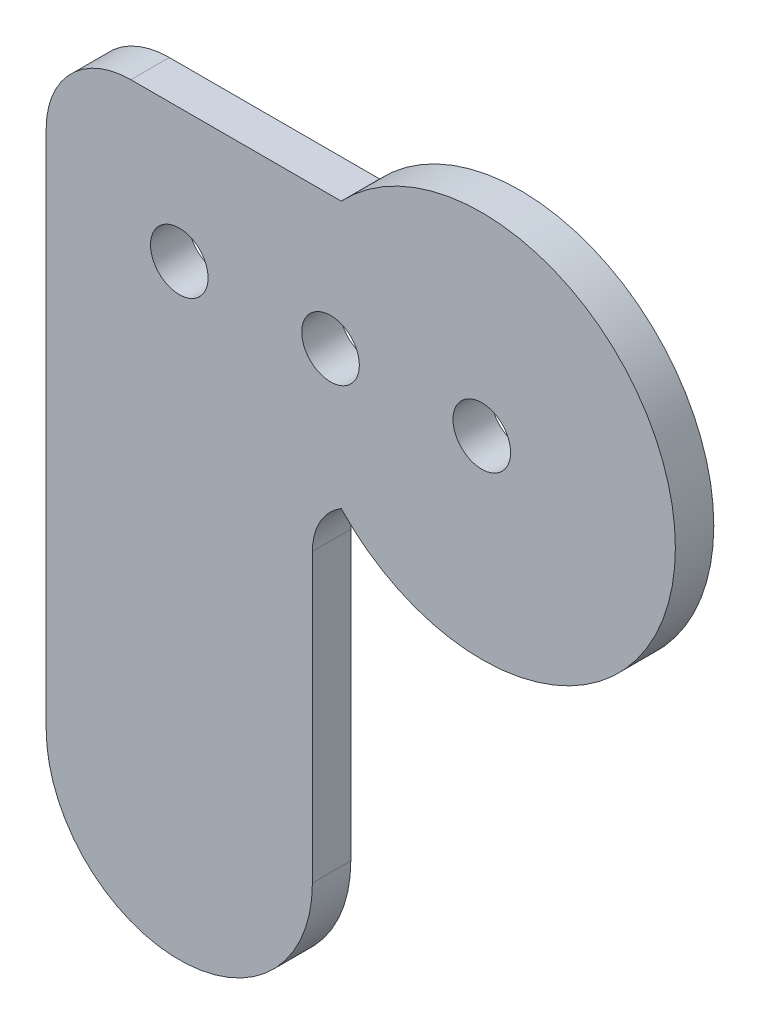
SolidWorks part; units mm, degrees
ref_plane "Front Plane" through (0, 0, 0) normal (0, 0, 1) x (1, 0, 0)
ref_plane "Top Plane" through (0, 0, 0) normal (0, 1, 0) x (1, 0, 0)
ref_plane "Right Plane" through (0, 0, 0) normal (1, 0, 0) x (0, 0, -1)
sketch "Sketch1" plane through (0, 0, 0) normal (0, 0, 1) x (1, 0, 0)
  line L0 (-11.619, 11) -> (-36, 11)
  line L1 (-36, 11) -> (-36, -39)
  line L2 (-14, -39) -> (-14, -11)
  line L3 (-14, -11) -> (-11.619, -11)
  arc A0 (-11.619, -11) -> (-11.619, 11) centre (0, 0) ccw
  arc A1 (-36, -39) -> (-14, -39) centre (-25, -39) ccw
  dimension "D1" = 32
  dimension "D7" = 25
  dimension "D2" = 11
  dimension "D3" = 11
  dimension "D4" = 39
  dimension "D6" = 22
extrude "Boss-Extrude1" add sketch "Sketch1" along normal blind 3.175
fillet "Fillet1" radius 7 1 edges at (-36, 11, 1.5875)
fillet "Fillet2" radius 5 1 edges at (-14, -11, 1.5875)
sketch "Sketch2" plane through (0, 0, 3.175) normal (0, 0, 1) x (1, 0, 0)
  circle A0 centre (0, 0) radius 2.3813
  dimension "D1" = 4.7625
extrude "Cut-Extrude1" cut sketch "Sketch2" against normal through all
pattern_linear "LPattern1" count 3 spacing 12.5 along (-1, 0, 0) of "Cut-Extrude1"
